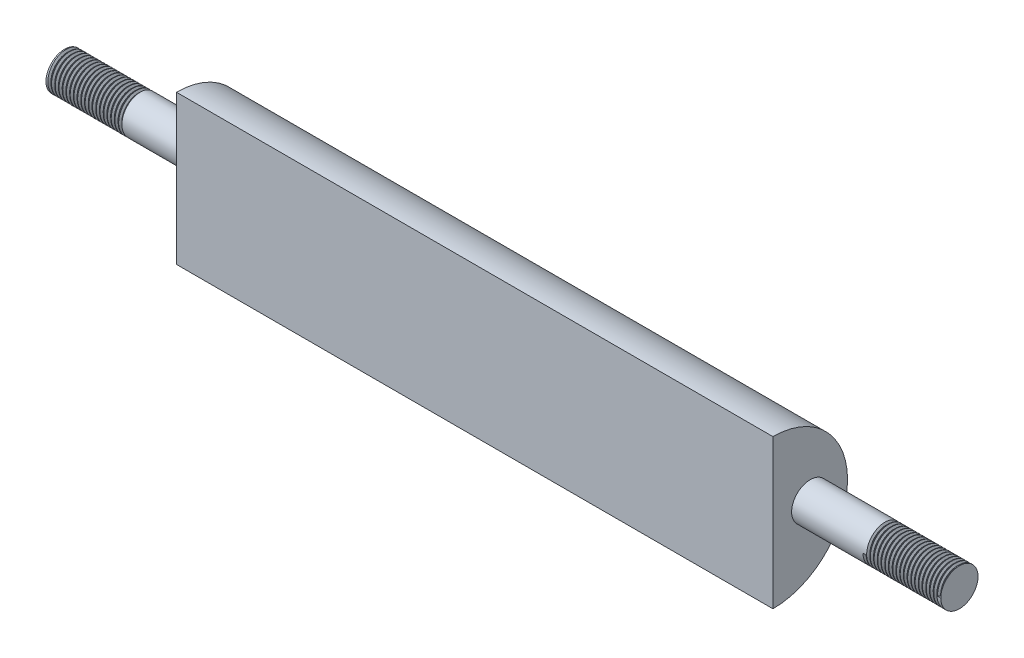
SolidWorks part; units mm, degrees
ref_plane "Front Plane" through (0, 0, 0) normal (0, 0, 1) x (1, 0, 0)
ref_plane "Top Plane" through (0, 0, 0) normal (0, 1, 0) x (1, 0, 0)
ref_plane "Right Plane" through (0, 0, 0) normal (1, 0, 0) x (0, 0, -1)
sketch "Sketch1" plane through (0, 0, 0) normal (1, 0, 0) x (0, 0, -1)
  line L0 (0, 5) -> (0, -5)
  arc A0 (0, -5) -> (0, 5) centre (0, 0) ccw
  dimension "D1" = 5
extrude "Boss-Extrude1" add sketch "Sketch1" along normal blind 40
sketch "Sketch2" plane through (40, 0, 0) normal (1, 0, 0) x (0, 0, -1)
  circle A0 centre (2.5, 0) radius 1.25
  dimension "D2" = 2.5
  dimension "D1" = 2.5
extrude "Boss-Extrude2" add sketch "Sketch2" along normal blind 10
sketch "Sketch4" plane through (0, 0, 0) normal (-1, 0, 0) x (0, 0, 1)
  circle A0 centre (-2.5, 0) radius 1.25
  dimension "D1" = 2.5
  dimension "D2" = 2.5
extrude "Boss-Extrude3" add sketch "Sketch4" along normal blind 10
thread "Thread3" pitch 0.25 method cut profile "Thread Profile4" start angle 0, offset 0, length 5, pitch 0.25, diameter 2.5
ref_plane "Plane4" through (50, 0, -1.25) normal (0, -1, 0) x (0, 0, 1)
sketch "Thread Profile4" plane through (50, 0, -1.25) normal (0, -1, 0) x (0, 0, 1)
  line L0 (0, 0) -> (0, 0.25) construction
  line L11 (0, 0) -> (0, 0.2187)
  line L12 (0, 0.2187) -> (-0.1353, 0.1406)
  line L13 (-0.1353, 0.1406) -> (-0.1353, 0.0781)
  line L15 (-0.1353, 0.0781) -> (0, 0)
  line L17 (-0.1353, 0.1094) -> (0, 0.1094) construction
  point P2 (0, 0)
  dimension "Pitch" = 0.25
  dimension "Profile_Angle" = 60
  dimension "Profile_Land" = 0.0625
  dimension "Profile_Height" = 0.1353
thread "Thread5" pitch 0.25 method cut profile "Thread Profile7" start angle 0, offset 0, length 5, pitch 0.25, diameter 2.5
ref_plane "Plane7" through (-10, 0, -3.75) normal (0, -1, 0) x (0, 0, -1)
sketch "Thread Profile7" plane through (-10, 0, -3.75) normal (0, -1, 0) x (0, 0, -1)
  line L0 (0, 0) -> (0, 0.25) construction
  line L11 (0, 0) -> (0, 0.2187)
  line L12 (0, 0.2187) -> (-0.1353, 0.1406)
  line L13 (-0.1353, 0.1406) -> (-0.1353, 0.0781)
  line L15 (-0.1353, 0.0781) -> (0, 0)
  line L17 (-0.1353, 0.1094) -> (0, 0.1094) construction
  point P2 (0, 0)
  dimension "Pitch" = 0.25
  dimension "Profile_Angle" = 60
  dimension "Profile_Land" = 0.0625
  dimension "Profile_Height" = 0.1353
